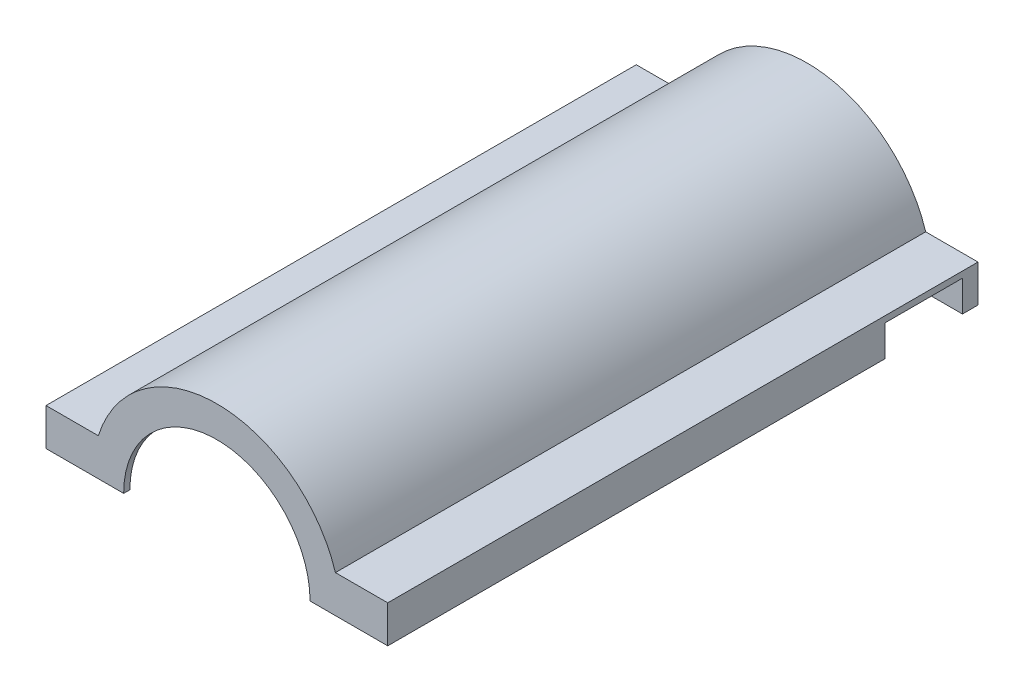
SolidWorks part; units mm, degrees
ref_plane "Front Plane" through (0, 0, 0) normal (0, 0, 1) x (1, 0, 0)
ref_plane "Top Plane" through (0, 0, 0) normal (0, 1, 0) x (1, 0, 0)
ref_plane "Right Plane" through (0, 0, 0) normal (1, 0, 0) x (0, 0, -1)
sketch "Sketch1" plane through (0, 0, 0) normal (0, 0, 1) x (1, 0, 0)
  line L0 (931.5757, 120) -> (1100, 120)
  line L1 (0, 0) -> (1100, 0)
  line L2 (0, 0) -> (0, 120)
  line L3 (0, 120) -> (168.4243, 120)
  line L4 (1100, 0) -> (1100, 120)
  arc A0 (931.5757, 120) -> (168.4243, 120) centre (550, 0) ccw
  dimension "D1" = 800
  dimension "D4" = 550
  dimension "D2" = 1100
  dimension "D3" = 120
extrude "Boss-Extrude1" add sketch "Sketch1" along normal blind 1900
sketch "Sketch2" plane through (0, 0, 1900) normal (0, 0, 1) x (1, 0, 0)
  line L0 (0, 0) -> (1100, 0) construction
  circle A0 centre (550, 0) radius 300
extrude "Cut-Extrude1" cut sketch "Sketch2" against normal through all
sketch "Sketch4" plane through (1100, 0, 0) normal (1, 0, 0) x (0, 0, -1)
  line L0 (-1900, 0) -> (0, 0) construction
  line L1 (-50, 0) -> (-300, 0)
  line L2 (-50, 0) -> (-50, 100)
  line L3 (-50, 100) -> (-300, 100)
  line L4 (-300, 0) -> (-300, 100)
  line L5 (0, 0) -> (0, 120) construction
  line L6 (-1900, 120) -> (0, 120) construction
  dimension "D1" = 250
  dimension "D2" = 50
  dimension "D3" = 20
extrude "Cut-Extrude3" cut sketch "Sketch4" against normal blind 550
shell "Shell1" thickness 20 removed face at (975, 0, 25) removed face at (125, 0, 950) removed face at (696.7752, 100.1826, 562.5) removed face at (975, 0, 1100)
